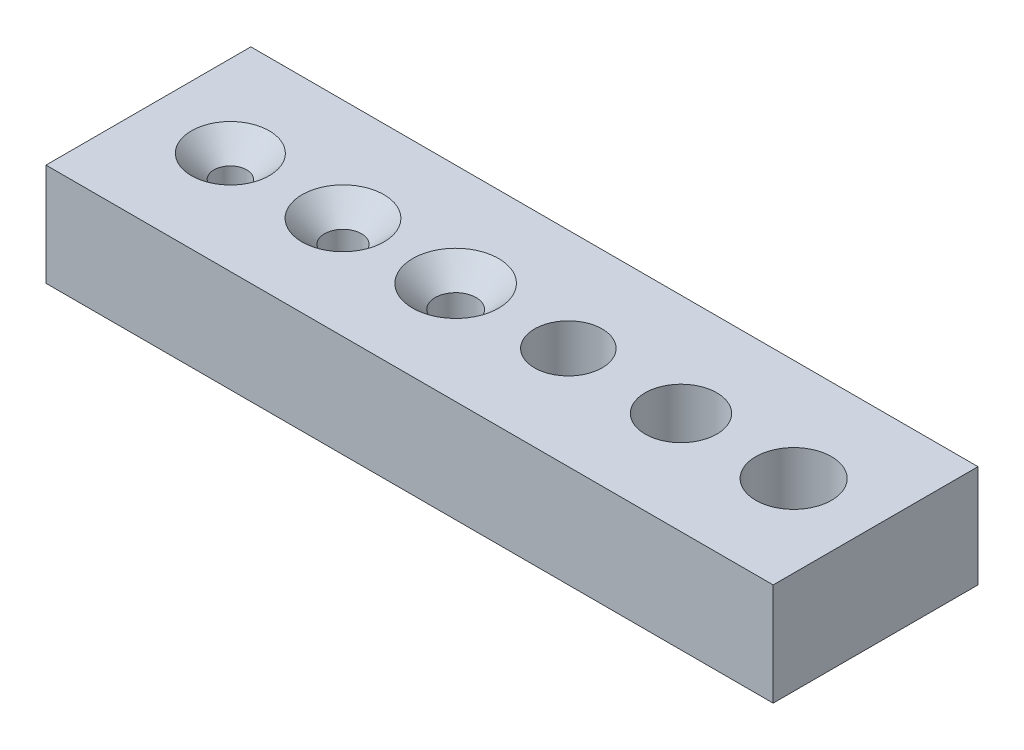
SolidWorks part; units mm, degrees
ref_plane "Front Plane" through (0, 0, 0) normal (0, 0, 1) x (1, 0, 0)
ref_plane "Top Plane" through (0, 0, 0) normal (0, 1, 0) x (1, 0, 0)
ref_plane "Right Plane" through (0, 0, 0) normal (1, 0, 0) x (0, 0, -1)
sketch "Sketch1" plane through (0, 0, 0) normal (0, 1, 0) x (1, 0, 0)
  line L1 (0, 0) -> (35.5, 0)
  line L2 (0, 0) -> (0, 10)
  line L3 (0, 10) -> (35.5, 10)
  line L4 (35.5, 0) -> (35.5, 10)
  dimension "D1" = 10
  dimension "D2" = 35.5
extrude "Boss-Extrude1" add sketch "Sketch1" along normal blind 5
sketch "Sketch2" plane through (0, 5, 0) normal (0, 1, 0) x (1, 0, 0)
  line L0 (0, 10) -> (0, 0) construction
  line L1 (0, 0) -> (35.5, 0) construction
  point P0 (4, 5)
  point P5 (9.5, 5)
  point P6 (31.5, 5)
  point P7 (15, 5)
  point P8 (20.5, 5)
  point P9 (26, 5)
  dimension "D1" = 4
  dimension "D2" = 5
  dimension "D3" = 5
  dimension "D4" = 2
hole_wizard "Tap Drill for M2x0.4 Tap1" positions "3DSketch1" profile "Sketch3" hole size "M2x0.4" standard "ANSI Metric"
sketch3d "3DSketch1"
  point P11 (9.5, 5, -5)
sketch "Sketch3" plane through (9.5, 5, -5) normal (1, 0, 0) x (0, 0, 1)
  line L0 (0, 0) -> (0, 7.5408)
  line L1 (0, 7.5408) -> (0.9, 7)
  line L2 (0.9, 7) -> (0.9, 1.1)
  line L3 (0.9, 1.1) -> (2, 0)
  line L5 (2, 0) -> (0, 0)
  line L6 (-0.9, 1.1) -> (-2, 0) construction
  line L10 (0, 7.5408) -> (-0.9, 7) construction
  line L11 (0, -6.35) -> (0, 107.95) construction
  dimension "Hole Dia." = 1.8
  dimension "Hole Depth" = 7
  dimension "Near C'Sink Dia." = 4
  dimension "Near C'Sink Angle" = 90
  dimension "Drill Angle" = 118
hole_wizard "Tap Drill for M2x0.4 Tap2" positions "3DSketch2" profile "Sketch4" hole size "M2x0.4" standard "ANSI Metric"
sketch3d "3DSketch2"
  point P4 (15, 5, -5)
sketch "Sketch4" plane through (15, 5, -5) normal (1, 0, 0) x (0, 0, 1)
  line L0 (0, 0) -> (0, 7.6009)
  line L1 (0, 7.6009) -> (1, 7)
  line L2 (1, 7) -> (1, 1.1)
  line L3 (1, 1.1) -> (2.1, 0)
  line L5 (2.1, 0) -> (0, 0)
  line L6 (-1, 1.1) -> (-2.1, 0) construction
  line L10 (0, 7.6009) -> (-1, 7) construction
  line L11 (0, -6.35) -> (0, 107.95) construction
  dimension "Hole Dia." = 2
  dimension "Hole Depth" = 7
  dimension "Near C'Sink Dia." = 4.2
  dimension "Near C'Sink Angle" = 90
  dimension "Drill Angle" = 118
hole_wizard "Tap Drill for M2x0.4 Tap3" positions "3DSketch3" profile "Sketch5" hole size "M2x0.4" standard "ANSI Metric"
sketch3d "3DSketch3"
  point P0 (4, 5, -5)
sketch "Sketch5" plane through (4, 5, -5) normal (1, 0, 0) x (0, 0, 1)
  line L0 (0, 0) -> (0, 7.4807)
  line L1 (0, 7.4807) -> (0.8, 7)
  line L2 (0.8, 7) -> (0.8, 1.1)
  line L3 (0.8, 1.1) -> (1.9, 0)
  line L5 (1.9, 0) -> (0, 0)
  line L6 (-0.8, 1.1) -> (-1.9, 0) construction
  line L10 (0, 7.4807) -> (-0.8, 7) construction
  line L11 (0, -6.35) -> (0, 107.95) construction
  dimension "Hole Dia." = 1.6
  dimension "Hole Depth" = 7
  dimension "Near C'Sink Dia." = 3.8
  dimension "Near C'Sink Angle" = 90
  dimension "Drill Angle" = 118
hole_wizard "Tap Drill for M4x0.7 Tap1" positions "3DSketch4" profile "Sketch6" hole size "M4x0.7" standard "ANSI Metric"
sketch3d "3DSketch4"
  point P0 (20.5, 5, -5)
sketch "Sketch6" plane through (20.5, 5, -5) normal (1, 0, 0) x (0, 0, 1)
  line L0 (0, 0) -> (0, 5.9914)
  line L1 (0, 5.9914) -> (1.65, 5)
  line L2 (1.65, 5) -> (1.65, 0)
  line L5 (1.65, 0) -> (0, 0)
  line L10 (0, 5.9914) -> (-1.65, 5) construction
  line L11 (0, -6.35) -> (0, 107.95) construction
  dimension "Hole Dia." = 3.3
  dimension "Hole Depth" = 5
  dimension "Drill Angle" = 118
hole_wizard "Tap Drill for M4x0.7 Tap2" positions "3DSketch5" profile "Sketch7" hole size "M4x0.7" standard "ANSI Metric"
sketch3d "3DSketch5"
  point P0 (26, 5, -5)
sketch "Sketch7" plane through (26, 5, -5) normal (1, 0, 0) x (0, 0, 1)
  line L0 (0, 0) -> (0, 6.0515)
  line L1 (0, 6.0515) -> (1.75, 5)
  line L2 (1.75, 5) -> (1.75, 0)
  line L5 (1.75, 0) -> (0, 0)
  line L10 (0, 6.0515) -> (-1.75, 5) construction
  line L11 (0, -6.35) -> (0, 107.95) construction
  dimension "Hole Dia." = 3.5
  dimension "Hole Depth" = 5
  dimension "Drill Angle" = 118
hole_wizard "Tap Drill for M4x0.7 Tap3" positions "3DSketch6" profile "Sketch8" hole size "M4x0.7" standard "ANSI Metric"
sketch3d "3DSketch6"
  point P0 (31.5, 5, -5)
sketch "Sketch8" plane through (31.5, 5, -5) normal (1, 0, 0) x (0, 0, 1)
  line L0 (0, 0) -> (0, 6.1116)
  line L1 (0, 6.1116) -> (1.85, 5)
  line L2 (1.85, 5) -> (1.85, 0)
  line L5 (1.85, 0) -> (0, 0)
  line L10 (0, 6.1116) -> (-1.85, 5) construction
  line L11 (0, -6.35) -> (0, 107.95) construction
  dimension "Hole Dia." = 3.7
  dimension "Hole Depth" = 5
  dimension "Drill Angle" = 118
